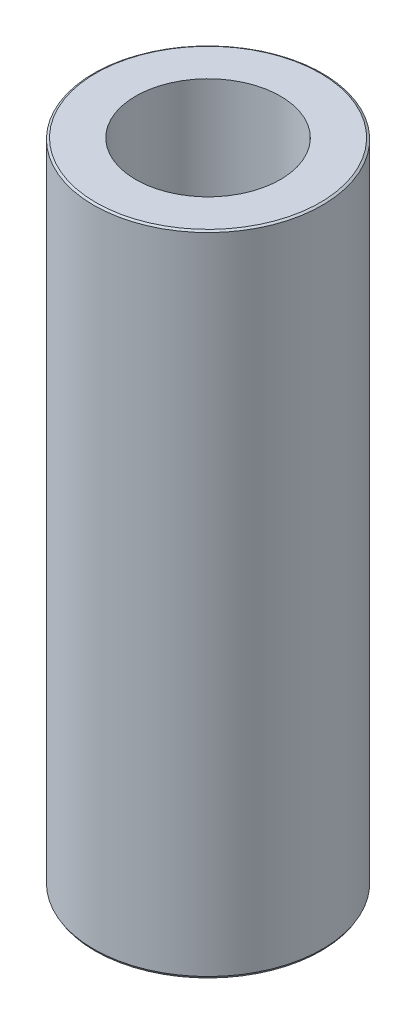
SolidWorks part; units mm, degrees
ref_plane "Front Plane" through (0, 0, 0) normal (0, 0, 1) x (1, 0, 0)
ref_plane "Top Plane" through (0, 0, 0) normal (0, 1, 0) x (1, 0, 0)
ref_plane "Right Plane" through (0, 0, 0) normal (1, 0, 0) x (0, 0, -1)
sketch "Sketch1" plane through (0, 0, 0) normal (0, 1, 0) x (1, 0, 0)
  circle A0 centre (0, 0) radius 45
  dimension "SHAFT_OD" = 90
extrude "Boss-Extrude1" add sketch "Sketch1" along normal blind 254.9823
sketch "Sketch2" plane through (0, 0, 0) normal (0, 1, 0) x (1, 0, 0)
  circle A0 centre (0, 0) radius 28.4907
  dimension "BORE_D" = 56.9813
extrude "Cut-Extrude1" cut sketch "Sketch2" along normal through all
chamfer "Chamfer1" distance 0.4924 angle 59.949 2 edges at (0, 254.9823, 45) (0, 0, 45) first distance on face at (0, 254.9823, 45) first distance on face at (0, 0, 28.4907)
